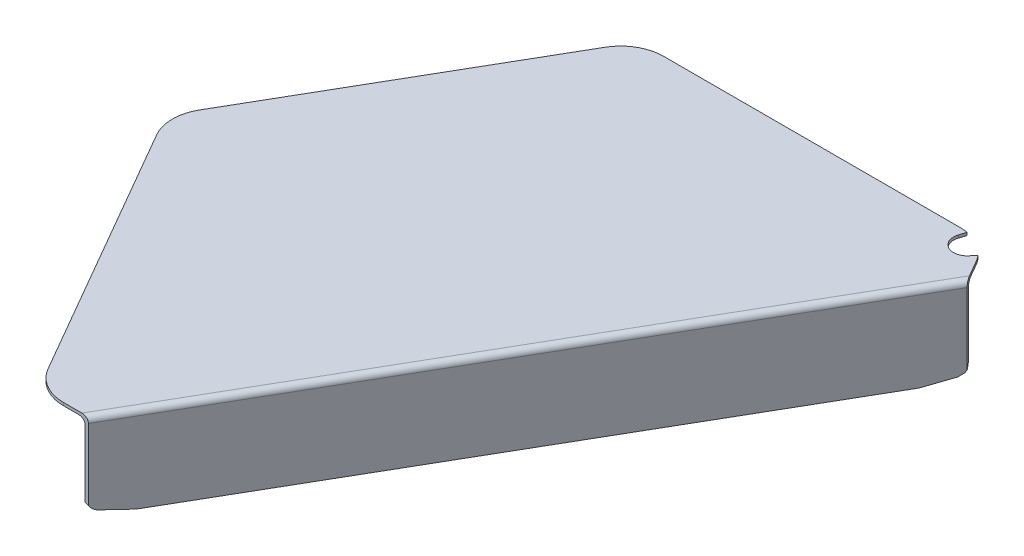
SolidWorks part; units mm, degrees
ref_plane "Alzado" through (0, 0, 0) normal (0, 0, 1) x (1, 0, 0)
ref_plane "Planta" through (0, 0, 0) normal (0, 1, 0) x (1, 0, 0)
ref_plane "Vista lateral" through (0, 0, 0) normal (1, 0, 0) x (0, 0, -1)
sketch "Croquis1" plane through (0, 0, 0) normal (0, 1, 0) x (1, 0, 0)
  line L0 (-63.1182, -98.8234) -> (-115.0797, -8.8234)
  line L1 (-115.0797, 6.1766) -> (-63.1182, 96.1766)
  line L2 (-50.1278, 103.6766) -> (53.7952, 103.6766)
  line L3 (71.1157, 88.6766) -> (66.7856, 96.1766)
  line L4 (-41.4676, -106.3234) -> (-50.1278, -106.3234)
  line L5 (103.3607, 144.5264) -> (-41.4676, -106.3234)
  line L13 (56.3584, 103.456) -> (55.6093, 101.1316)
  line L14 (63.9317, 96.7848) -> (65.2421, 98.3704)
  arc A0 (-115.0797, 6.1766) -> (-115.0797, -8.8234) centre (-102.0893, -1.3234) ccw
  arc A1 (-50.1278, 103.6766) -> (-63.1182, 96.1766) centre (-50.1278, 88.6766) ccw
  arc A2 (66.7856, 96.1766) -> (65.2421, 98.3704) centre (53.7952, 88.6766) ccw
  arc A3 (-63.1182, -98.8234) -> (-50.1278, -106.3234) centre (-50.1278, -91.3234) ccw
  arc A4 (56.3584, 103.456) -> (53.7952, 103.6766) centre (53.7952, 88.6766) ccw
  arc A9 (55.6093, 101.1316) -> (63.9317, 96.7848) centre (60.1426, 99.6706) ccw
  dimension "D1" = 103.923
  dimension "D2" = 103.923
  dimension "D3" = 103.923
  dimension "D4" = 120
extrude "Saliente-Extruir1" add sketch "Croquis1" along normal blind 1 contours L0 A3 L4 L5 L3 A2 L2 A1 L1 A0 region at (-31.5151, 0, -17.5988)
sketch "Croquis2" plane through (0, 0, 0) normal (0, -1, 0) x (1, 0, 0)
  line L0 (71.1157, -88.6766) -> (-41.4676, 106.3234) construction
  line L1 (71.1157, -88.6766) -> (-41.4676, 106.3234)
  line L3 (-41.4676, 106.3234) -> (-50.1278, 106.3234) construction
  line L4 (71.1157, -88.6766) -> (66.7856, -96.1766) construction
  line L5 (71.1157, -88.6766) -> (70.5384, -89.6766)
  line L6 (-42.6223, 106.3234) -> (70.5384, -89.6766)
  line L7 (-41.4676, 106.3234) -> (-42.6223, 106.3234)
  line L8 (71.1157, -88.6766) -> (70.5384, -89.6766)
  line M19 (66.7856, -96.1766) -> (71.1157, -88.6766)
  line M20 (71.1157, -88.6766) -> (-41.4676, 106.3234)
  line M21 (-41.4676, 106.3234) -> (-50.1278, 106.3234)
  dimension "D1" = 1
extrude "Saliente-Extruir2" add sketch "Croquis2" along normal blind 31 contours L6 M21 M19 M20 region at (14.3907, 0, 8.5732)
fillet "Redondeo1" radius 2 2 edges at (14.8241, 1, 8.8234) (13.9581, 0, 8.3234)
sketch "Croquis3" plane through (14.9387, 0, 8.6249) normal (0.866, 0, 0.5) x (0.5, 0, -0.866)
  line L13 (-113.5631, -25.2477) -> (-125.0743, -30.3477)
  line L14 (100.0565, -29.2) -> (110.0507, -27.654)
  line L15 (112.9314, -24.6279) -> (112.5471, -25.7751)
  line L16 (112.9314, -31) -> (112.9314, -2) construction
  line L19 (112.9314, -24.6279) -> (140.2294, -2.7085)
  line L20 (112.5471, -25.7751) -> (111.8206, -26.6938)
  line L21 (111.8206, -26.6938) -> (110.8637, -27.1868)
  line L22 (110.8637, -27.1868) -> (110.0507, -27.654)
  line L23 (-33.7155, -29.2) -> (-40.2304, -29.2) construction
  line L24 (-100.515, -29.2) -> (-110.7107, -27.5888)
  line L25 (-110.7107, -27.5888) -> (-111.8314, -27.0235)
  line L26 (-111.8314, -27.0235) -> (-112.96, -25.8477)
  line L34 (100.0565, -29.2) -> (-100.515, -29.2)
  line L35 (140.2294, -2.7085) -> (121.2929, -43.8284)
  line L36 (121.2929, -43.8284) -> (-113.2262, -43.8284)
  line L37 (-113.2262, -43.8284) -> (-125.0743, -30.3477)
  line L38 (-112.96, -25.8477) -> (-113.5631, -25.2477)
  line L39 (-113.5631, -23.8967) -> (-113.5631, -30.2) construction
  ellipse E2 centre (100.0565, -4.2) end of major axis (71.189, -4.2) minor radius 25 (100.0565, -29.2) -> (110.2523, -27.5888) ccw construction
  ellipse E3 centre (104.8485, -4.2) end of major axis (104.8485, 20.8) minor radius 15.2998 (110.2523, -27.5888) -> (115.9756, -21.3587) ccw construction
  ellipse E4 centre (-100.515, -4.2) end of major axis (-129.3825, -4.2) minor radius 25 (-110.7107, -27.5888) -> (-100.515, -29.2) ccw construction
  ellipse E5 centre (-105.307, -4.2) end of major axis (-105.307, 20.8) minor radius 15.2998 (-116.4341, -21.3587) -> (-110.7107, -27.5888) ccw construction
  spline S0 degree 3 poles (113.1046, -23.8967) (113.1046, -24.3152) (113.0222, -24.7208) (112.8006, -25.3054) (112.7116, -25.492) (112.506, -25.8504) (112.3886, -26.0232) (112.001, -26.5113) (111.7001, -26.7942) (111.0173, -27.2728) (110.6491, -27.459) (110.2523, -27.5888) knots 0 0 0 0 0.25 0.25 0.375 0.375 0.5 0.5 0.75 0.75 1 1 1 1 construction
  spline S1 degree 3 poles (111.3727, -27.0237) (111.4171, -26.9921) (111.4982, -26.9344) (111.6778, -26.8029) (111.9513, -26.5953) (112.242, -26.3599) (112.487, -26.151) (112.6499, -26.0078) (112.7914, -25.8801) (112.9217, -25.7599) (113.049, -25.6398) (113.1813, -25.5121) (113.3122, -25.3828) (113.4354, -25.2585) (113.6428, -25.0447) (113.9597, -24.7041) (114.3536, -24.2495) (114.7543, -23.7543) (115.1224, -23.2688) (115.4511, -22.8057) (115.7764, -22.3222) (116.1962, -21.6657) (116.5192, -21.0924) (116.7205, -20.735) knots 0 0 0 0 0.0216 0.03951 0.087453 0.155278 0.184722 0.210029 0.233539 0.255739 0.279179 0.302701 0.326302 0.348434 0.367881 0.437015 0.520307 0.586413 0.665021 0.735297 0.783715 0.865208 1 1 1 1 construction
  spline S2 degree 3 poles (-117.1789, -20.735) (-117.111, -20.8581) (-116.9823, -21.0918) (-116.795, -21.4151) (-116.6268, -21.6965) (-116.4785, -21.937) (-116.3513, -22.1382) (-116.2457, -22.3017) (-116.1576, -22.4358) (-116.0598, -22.5824) (-115.8749, -22.8545) (-115.5809, -23.2688) (-115.1452, -23.8434) (-114.6191, -24.482) (-114.03, -25.1285) (-113.3996, -25.7521) (-112.8494, -26.2398) (-112.3966, -26.6053) (-112.1363, -26.8029) (-111.9567, -26.9344) (-111.8755, -26.9921) (-111.8311, -27.0237) knots 0 0 0 0 0.045961 0.087212 0.123711 0.155418 0.182301 0.204333 0.221703 0.237142 0.264734 0.335013 0.413623 0.519211 0.632154 0.735329 0.850998 0.912553 0.960488 0.978399 1 1 1 1 construction
  spline S3 degree 3 poles (-110.7107, -27.5888) (-111.1082, -27.4588) (-111.4751, -27.2728) (-111.9836, -26.9171) (-112.1467, -26.7845) (-112.4482, -26.501) (-112.5878, -26.3495) (-112.8446, -26.0264) (-112.9627, -25.8534) (-113.1696, -25.493) (-113.2582, -25.307) (-113.4043, -24.9229) (-113.462, -24.7248) (-113.5418, -24.3148) (-113.5631, -24.1063) (-113.5631, -23.8967) knots 0 0 0 0 0.25 0.25 0.375 0.375 0.5 0.5 0.625 0.625 0.75 0.75 0.875 0.875 1 1 1 1 construction
  point P16 (-125.0743, -30.3477)
  point P58 (-113.7052, -25.097)
extrude "Cortar-Extruir1" cut sketch "Croquis3" against normal blind 6
